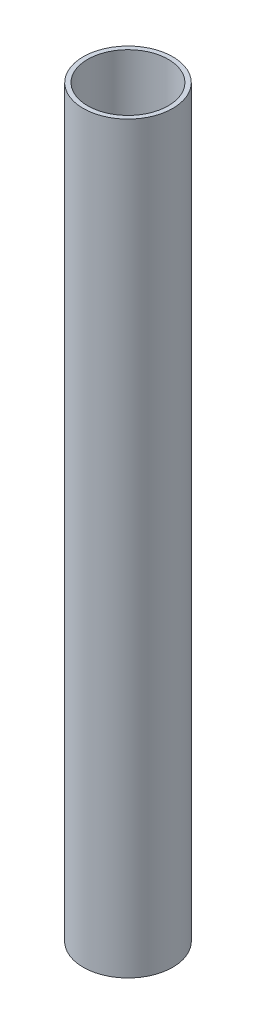
SolidWorks part; units mm, degrees
other "Boss-Extrude"
material "Toray T700"
ref_plane "Front" through (0, 0, 0) normal (0, 0, 1) x (1, 0, 0)
ref_plane "Top" through (0, 0, 0) normal (0, 1, 0) x (1, 0, 0)
ref_plane "Right" through (0, 0, 0) normal (1, 0, 0) x (0, 0, -1)
sketch "Sketch1" plane through (0, 0, 0) normal (0, 1, 0) x (1, 0, 0)
  line L5 (4.7969, 0) -> (-5.97, 0) construction
  circle A0 centre (0, 0) radius 10
  circle A1 centre (0, 0) radius 9
  dimension "D1" = 20
  dimension "D2" = 18
extrude "Boss-Extrude1" add sketch "Sketch1" along normal blind 166.1
ref_axis "Axis1" through (0, 0, 50) along (0, 0, -1)
